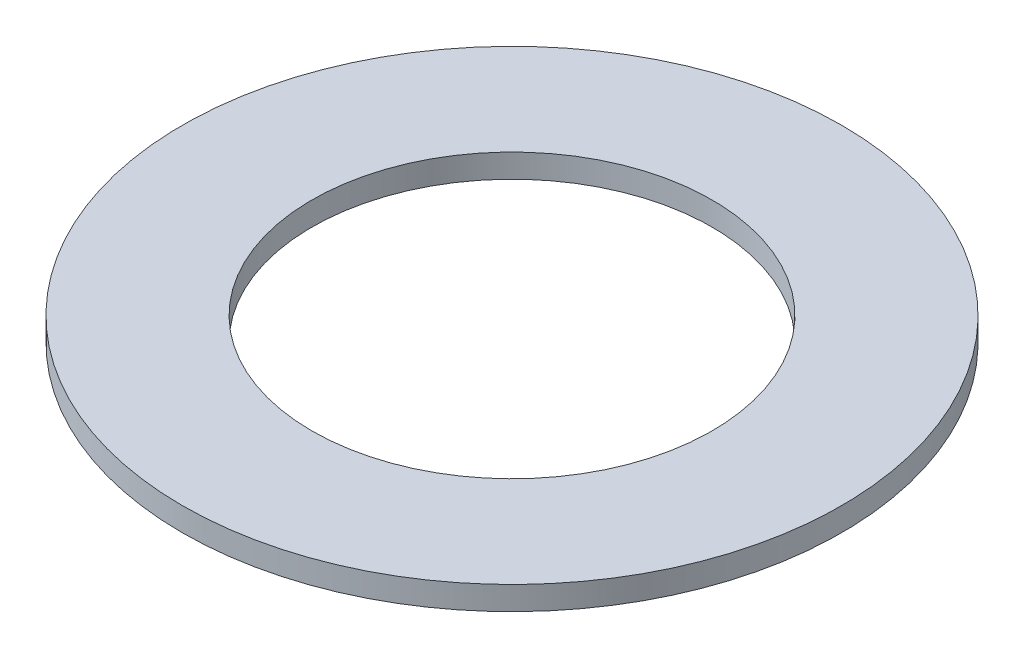
SolidWorks part; units mm, degrees
ref_plane "Front Plane" through (0, 0, 0) normal (0, 0, 1) x (1, 0, 0)
ref_plane "Top Plane" through (0, 0, 0) normal (0, 1, 0) x (1, 0, 0)
ref_plane "Right Plane" through (0, 0, 0) normal (1, 0, 0) x (0, 0, -1)
sketch "Sketch1" plane through (0, 0, 0) normal (0, 1, 0) x (1, 0, 0)
  circle A0 centre (0, 0) radius 70
  dimension "FLANGE_OD" = 140
extrude "Boss-Extrude1" add sketch "Sketch1" along normal blind 5
sketch "Sketch2" plane through (0, 0, 0) normal (0, 1, 0) x (1, 0, 0)
  circle A0 centre (0, 0) radius 42.5
  dimension "BORE_D" = 85
extrude "Cut-Extrude1" cut sketch "Sketch2" along normal through all
sketch "Sketch3" plane through (0, 5, 0) normal (0, 1, 0) x (1, 0, 0)
  circle A0 centre (0, 0) radius 27.9356 construction
  circle A1 centre (-27.9356, 0) radius 3.3725
  dimension "BOLT_D" = 6.745
  dimension "BOLT_PCD" = 55.8712
extrude "Cut-Extrude2" cut sketch "Sketch3" against normal blind 3.4166 rebuild error yes
pattern_circular "CirPattern1" count 6 over 360 rebuild error yes
